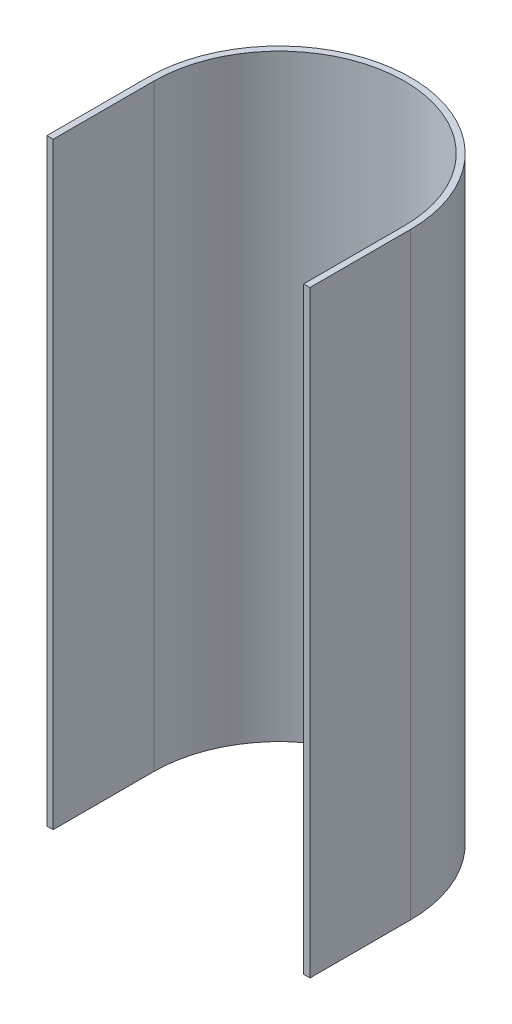
SolidWorks part; units mm, degrees
material "PE High Density Film"
ref_plane "Ebene vorne" through (0, 0, 0) normal (0, 0, 1) x (1, 0, 0)
ref_plane "Ebene oben" through (0, 0, 0) normal (0, 1, 0) x (1, 0, 0)
ref_plane "Ebene rechts" through (0, 0, 0) normal (1, 0, 0) x (0, 0, -1)
sketch "Sketch1" plane through (0, 0, 0) normal (0, 1, 0) x (1, 0, 0)
  line L0 (22.5293, 3) -> (22.5293, -0.2)
  line L1 (22.5293, -0.2) -> (30.8893, -0.2)
  line L2 (22.7293, 3) -> (22.7293, 0)
  line L3 (22.7293, 0) -> (30.6893, 0)
  line L4 (30.6893, 3) -> (30.6893, 0)
  line L5 (22.7293, 3) -> (30.6893, 0) construction
  line L6 (22.7293, 0) -> (30.6893, 3) construction
  line L7 (30.8893, 3) -> (30.8893, -0.2)
  line L8 (30.6893, 0) -> (30.6893, -0.2)
  line L9 (22.7293, 0) -> (22.7293, -0.2)
  line L10 (30.8893, -0.2) -> (30.8893, 0)
  line L11 (30.8893, -0.2) -> (31.0893, -0.2)
  line L12 (30.8893, 0) -> (31.0893, 0)
  line L13 (31.0893, -0.2) -> (31.0893, 0)
  line L14 (26.7093, 3) -> (26.7093, 0) construction
  line L15 (22.5293, 3) -> (22.5293, -0.2)
  line L16 (22.5293, -0.2) -> (22.3293, -0.2)
  line L17 (22.3293, -0.2) -> (22.3293, 0)
  line L18 (22.5293, 0) -> (22.3293, 0)
  arc A0 (30.6893, 3) -> (22.7293, 3) centre (26.7093, 3) ccw
  arc A1 (30.8893, 3) -> (22.5293, 3) centre (26.7093, 3) ccw
  point P0 (26.7093, 1.5)
  dimension "D1" = 0
  dimension "D2" = 7.96
  dimension "D3" = 3
  dimension "D5" = 0.2
  dimension "D6" = 0.2
  dimension "D7" = 3
  dimension "D4" = 0.2
extrude "Boss-Extrude1" add sketch "Sketch1" along normal blind 18 contours L7 A1 L0 L15 L1 L9 L2 A0 L4 L8 region at (26.7093, 0, -7.0685)
extrude "Boss-Extrude2" add sketch "Sketch1<4>" against normal blind 1 contours L7 A1 L0 L15 L1 L9 L2 A0 L4 L8 region at (26.7093, 0, -7.0685)
sketch "Sketch1<4>" plane through (0, 0, 0) normal (0, 1, 0) x (1, 0, 0) same geometry as "Sketch1"
equation "\"D7@Sketch1\"=\"D3@Sketch1\""
